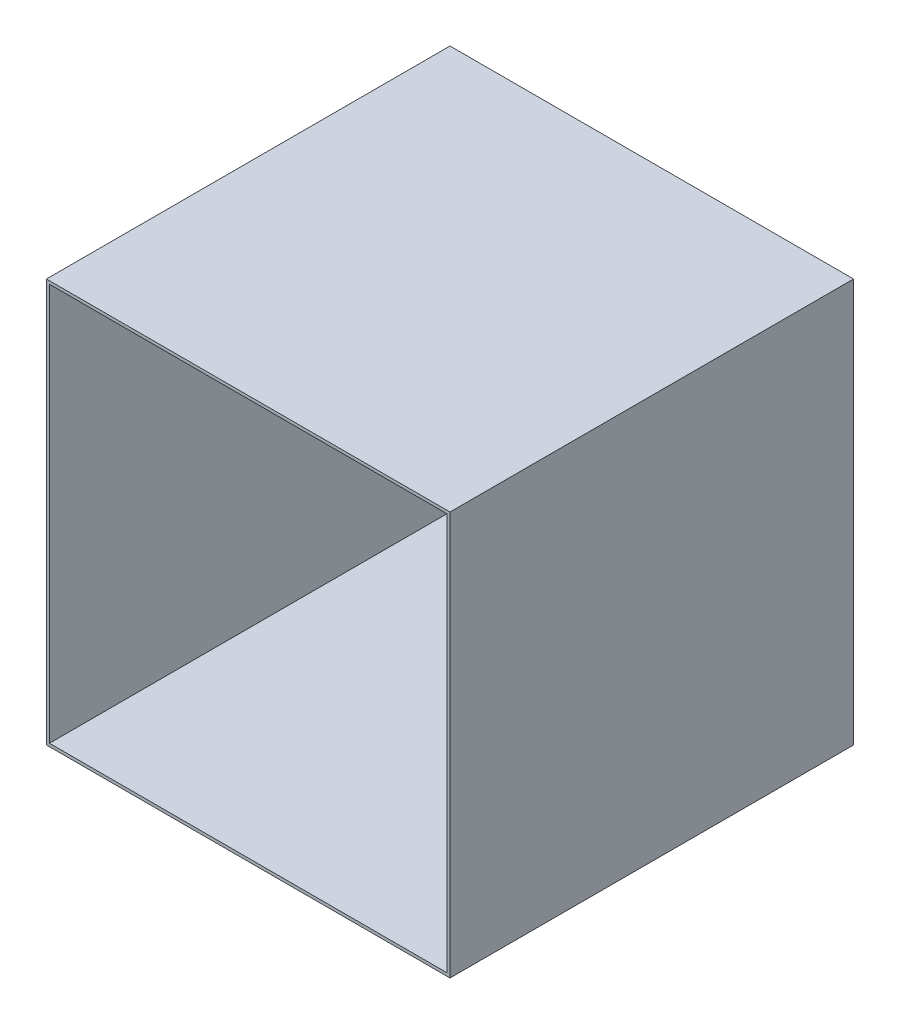
SolidWorks part; units mm, degrees
material "AISI 304"
ref_plane "Alzado" through (0, 0, 0) normal (0, 0, 1) x (1, 0, 0)
ref_plane "Planta" through (0, 0, 0) normal (0, 1, 0) x (1, 0, 0)
ref_plane "Vista lateral" through (0, 0, 0) normal (1, 0, 0) x (0, 0, -1)
sketch "Croquis1" plane through (0, 0, 0) normal (0, 0, 1) x (1, 0, 0)
  line L1 (0, 0) -> (80, 0)
  line L2 (0, 0) -> (0, 80)
  line L3 (0, 80) -> (80, 80)
  line L4 (80, 0) -> (80, 80)
  dimension "D1" = 80
  dimension "D2" = 80
extrude "Saliente-Extruir1" add sketch "Croquis1" along normal blind 80
shell "Vaciado1" thickness 0.6 removed face at (40, 40, 0) removed face at (40, 40, 80)
